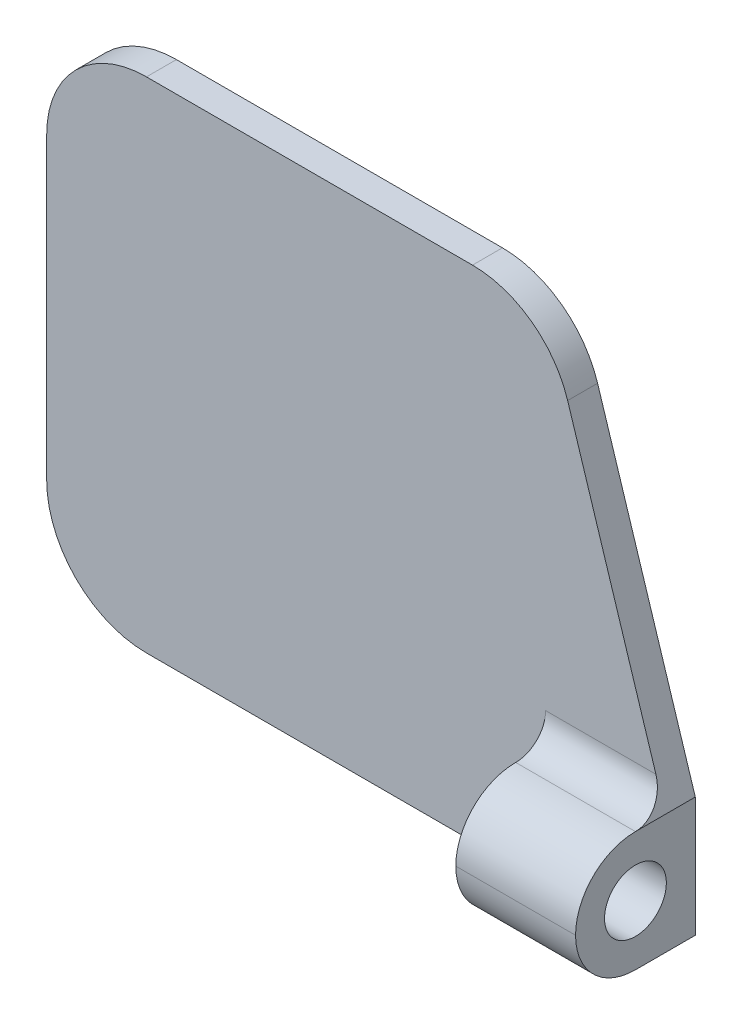
SolidWorks part; units mm, degrees
ref_plane "Face" through (0, 0, 0) normal (0, 0, 1) x (1, 0, 0)
ref_plane "Dessus" through (0, 0, 0) normal (0, 1, 0) x (1, 0, 0)
ref_plane "Droite" through (0, 0, 0) normal (1, 0, 0) x (0, 0, -1)
sketch "Esquisse1" plane through (0, 0, 0) normal (0, 0, 1) x (1, 0, 0)
  line L1 (0, 0) -> (50, 0)
  line L2 (0, 0) -> (0, 50)
  line L3 (0, 50) -> (50, 50)
  line L4 (50, 0) -> (50, 50)
  dimension "D1" = 50
  dimension "D2" = 50
extrude "Boss.-Extru.1" add sketch "Esquisse1" along normal blind 3
sketch "Esquisse2" plane through (0, 0, 3) normal (0, 0, 1) x (1, 0, 0)
  line L0 (50, 0) -> (62, 0)
  line L1 (62, 0) -> (62, 12)
  line L2 (62, 12) -> (50, 50)
  line L3 (50, 50) -> (50, 0)
  dimension "D1" = 12
  dimension "D2" = 12
extrude "Boss.-Extru.2" add sketch "Esquisse2" against normal up to vertex (3 mm away) up to point (50, 0, 0)
sketch "Esquisse3" plane through (0, 0, 3) normal (0, 0, 1) x (1, 0, 0)
  line L5 (62, 0) -> (50, 0)
  line L6 (62, 0) -> (62, 12)
  line L7 (62, 12) -> (50, 12)
  line L8 (50, 0) -> (50, 12)
extrude "Boss.-Extru.3" add sketch "Esquisse3" along normal blind 9
sketch "Esquisse4" plane through (62, 0, 0) normal (1, 0, 0) x (0, 0, -1)
  line L0 (-6, 12) -> (-6, 0) construction
  line L2 (0, 0) -> (-12, 0) construction
  line L3 (-12, 12) -> (-3, 12) construction
  circle A0 centre (-6, 6) radius 3.1
  dimension "D1" = 6.2
extrude "Enlèv. mat.-Extru.1" cut sketch "Esquisse4" against normal blind 10
fillet "Congé1" radius 6 2 edges at (56, 0, 12) (56, 12, 12)
fillet "Congé2" radius 3 1 edges at (56, 12, 3)
fillet "Congé3" radius 10 3 edges at (0, 0, 1.5) (0, 50, 1.5) (50, 50, 1.5)
